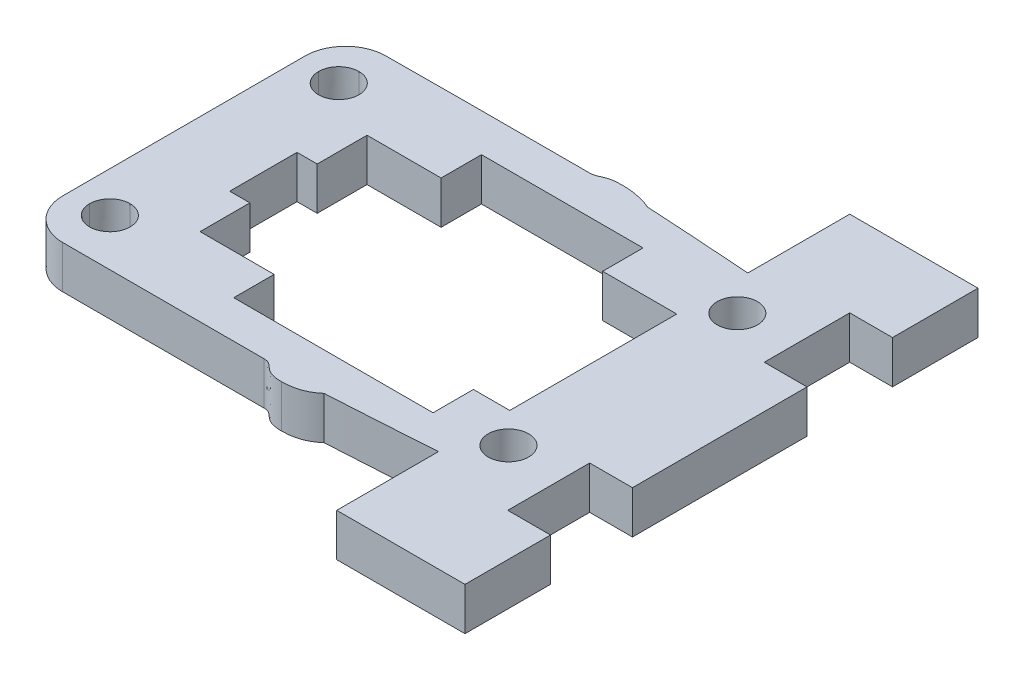
SolidWorks part; units mm, degrees
ref_plane "Front Plane" through (0, 0, 0) normal (0, 0, 1) x (1, 0, 0)
ref_plane "Top Plane" through (0, 0, 0) normal (0, 1, 0) x (1, 0, 0)
ref_plane "Right Plane" through (0, 0, 0) normal (1, 0, 0) x (0, 0, -1)
sketch "Sketch1" plane through (0, 0, 0) normal (0, 1, 0) x (1, 0, 0)
  line L0 (117.4101, 18.6303) -> (141.91, 18.6303) construction
  line L1 (141.91, 37.6804) -> (151.435, 37.6804)
  line L2 (141.91, 37.6804) -> (141.91, 30.1038)
  line L3 (141.91, -0.4196) -> (151.435, -0.4196)
  line L4 (151.435, 37.6804) -> (151.435, 31.3304)
  line L5 (151.435, 18.6304) -> (146.6846, 18.6304) construction
  line L6 (151.435, 31.3304) -> (148.26, 31.3304)
  line L7 (148.26, 24.9804) -> (148.26, 31.3304)
  line L8 (148.26, 24.9804) -> (151.435, 24.9804)
  line L9 (151.435, 24.9804) -> (151.435, 12.0177)
  line L10 (151.435, 12.0177) -> (148.26, 12.0177)
  line L11 (148.26, 12.0177) -> (148.26, 5.9304)
  line L12 (148.26, 5.9304) -> (151.435, 5.9304)
  line L14 (151.435, 5.9304) -> (151.435, -0.4196)
  line L15 (141.91, 24.8303) -> (141.91, 12.4303)
  line L16 (141.91, 7.1413) -> (141.91, -0.4196)
  line L576 (111.51, 9.6305) -> (111.51, 27.6303)
  line L578 (117.4101, 16.1303) -> (118.91, 16.1303)
  line L579 (118.91, 16.1303) -> (118.91, 12.4303)
  line L580 (118.91, 12.4303) -> (124.41, 12.4303)
  line L581 (124.41, 12.4303) -> (124.41, 9.4305)
  line L582 (124.41, 9.4305) -> (139.21, 9.4305)
  line L583 (139.21, 9.4305) -> (139.21, 12.4303)
  line L584 (139.21, 12.4303) -> (141.91, 12.4303)
  line L586 (141.91, 24.8303) -> (136.41, 24.8303)
  line L587 (136.41, 24.8303) -> (136.41, 27.8303)
  line L588 (136.41, 27.8303) -> (124.41, 27.8303)
  line L589 (124.41, 27.8303) -> (124.41, 24.8303)
  line L590 (124.41, 24.8303) -> (118.91, 24.8303)
  line L591 (118.91, 24.8303) -> (118.91, 21.1303)
  line L592 (118.91, 21.1303) -> (117.4101, 21.1303)
  line L593 (117.4101, 21.1303) -> (117.4101, 16.1303)
  circle A0 centre (144.11, 10.1304) radius 1.4998
  circle A1 centre (144.1101, 27.1303) radius 1.4999
  spline S312 degree 3 poles (116.01, 27.1303) (116.01, 26.3018) (115.3385, 25.6303) (114.5101, 25.6303) knots 0 0 0 0 0.2 0.2 0.2 0.2
  spline S313 degree 3 poles (114.5101, 25.6303) (113.6816, 25.6302) (113.0101, 26.3018) (113.0101, 27.1302) knots 0.2 0.2 0.2 0.2 0.4 0.4 0.4 0.4
  spline S314 degree 3 poles (113.0101, 27.1302) (113.01, 27.9587) (113.6816, 28.6302) (114.51, 28.6303) knots 0.4 0.4 0.4 0.4 0.6 0.6 0.6 0.6
  spline S315 degree 3 poles (114.51, 28.6303) (115.3385, 28.6303) (116.01, 27.9587) (116.01, 27.1303) knots 0.6 0.6 0.6 0.6 1 1 1 1
  spline S320 degree 3 poles (116.01, 10.1305) (116.01, 9.3021) (115.3384, 8.6304) (114.5101, 8.6304) knots 0 0 0 0 0.2 0.2 0.2 0.2
  spline S321 degree 3 poles (114.5101, 8.6304) (113.6817, 8.6304) (113.01, 9.3021) (113.01, 10.1304) knots 0.2 0.2 0.2 0.2 0.4 0.4 0.4 0.4
  spline S322 degree 3 poles (113.01, 10.1304) (113.01, 10.9588) (113.6817, 11.6303) (114.51, 11.6303) knots 0.4 0.4 0.4 0.4 0.6 0.6 0.6 0.6
  spline S323 degree 3 poles (114.51, 11.6303) (115.3384, 11.6303) (116.01, 10.9588) (116.01, 10.1305) knots 0.6 0.6 0.6 0.6 1 1 1 1
  spline S328 degree 3 poles (111.51, 27.6303) (111.51, 28.4259) (111.8262, 29.189) (112.3888, 29.7516) knots 0.058824 0.058824 0.058824 0.058824 0.117647 0.117647 0.117647 0.117647
  spline S329 degree 3 poles (112.3888, 29.7516) (112.9514, 30.3142) (113.7144, 30.6303) (114.51, 30.6303) knots 0.117647 0.117647 0.117647 0.117647 0.176471 0.176471 0.176471 0.176471
  spline S330 degree 3 poles (114.51, 30.6303) (114.4972, 30.6508) (123.8342, 30.6751) (129.5578, 30.6658) knots 0.176471 0.176471 0.176471 0.176471 0.235294 0.235294 0.235294 0.235294
  spline S331 degree 3 poles (129.5578, 30.6658) (130.305, 30.6646) (130.244, 31.1022) (131.5888, 31.1022) knots 0.235294 0.235294 0.235294 0.235294 0.294118 0.294118 0.294118 0.294118
  spline S332 degree 3 poles (131.5888, 31.1022) (133.0006, 31.1022) (133.901, 30.6448) (133.91, 30.6303) knots 0.294118 0.294118 0.294118 0.294118 0.352941 0.352941 0.352941 0.352941
  spline S333 degree 2 poles (133.91, 30.6303) (138.0156, 30.4001) (141.91, 30.1038) knots 0.352941 0.352941 0.352941 0.400841 0.400841 0.400841
  spline S336 degree 2 poles (141.91, 7.1413) (138.0126, 6.8547) (133.91, 6.6305) knots 0.600436 0.600436 0.600436 0.647059 0.647059 0.647059
  spline S337 degree 2 poles (133.91, 6.6305) (132.9823, 5.8019) (131.5888, 5.8019) knots 0.647059 0.647059 0.647059 0.705882 0.705882 0.705882
  spline S338 degree 3 poles (131.5888, 5.8019) (130.0782, 5.8019) (130.2699, 6.6305) (129.4696, 6.6305) knots 0.705882 0.705882 0.705882 0.705882 0.764706 0.764706 0.764706 0.764706
  spline S339 degree 2 poles (129.4696, 6.6305) (123.7428, 6.6305) (114.51, 6.6305) knots 0.764706 0.764706 0.764706 0.823529 0.823529 0.823529
  spline S340 degree 3 poles (114.51, 6.6305) (113.7144, 6.6305) (112.9514, 6.9465) (112.3888, 7.5091) knots 0.823529 0.823529 0.823529 0.823529 0.882353 0.882353 0.882353 0.882353
  spline S341 degree 3 poles (112.3888, 7.5091) (111.8262, 8.0717) (111.51, 8.8348) (111.51, 9.6305) knots 0.882353 0.882353 0.882353 0.882353 1 1 1 1
  dimension "D1" = 9.525
  dimension "D2" = 38.1
  dimension "D4" = 3.175
  dimension "D5" = 6.35
  dimension "D6" = 3.175
  dimension "D7" = 6.35
  dimension "D8" = 6.35
extrude "Boss-Extrude1" add sketch "Sketch1" along normal blind 3.175
